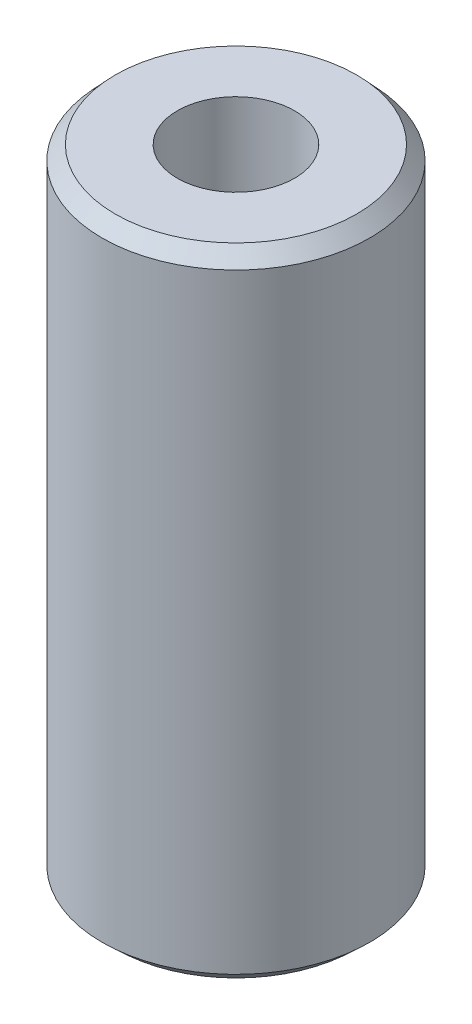
SolidWorks part; units mm, degrees
ref_plane "Front Plane" through (0, 0, 0) normal (0, 0, 1) x (1, 0, 0)
ref_plane "Top Plane" through (0, 0, 0) normal (0, 1, 0) x (1, 0, 0)
ref_plane "Right Plane" through (0, 0, 0) normal (1, 0, 0) x (0, 0, -1)
sketch "Sketch1" plane through (0, 0, 0) normal (0, 1, 0) x (1, 0, 0)
  circle A0 centre (0, 0) radius 22.5
  dimension "SHAFT_OD" = 45
extrude "Boss-Extrude1" add sketch "Sketch1" along normal blind 107.1898
sketch "Sketch2" plane through (0, 0, 0) normal (0, 1, 0) x (1, 0, 0)
  circle A0 centre (0, 0) radius 9.8542
  dimension "BORE_D" = 19.7083
extrude "Cut-Extrude1" cut sketch "Sketch2" along normal through all
chamfer "Chamfer1" distance 2.3831 angle 42.856 2 edges at (0, 107.1898, 22.5) (0, 0, 22.5) first distance on face at (0, 107.1898, 22.5) first distance on face at (0, 0, 9.8542)
